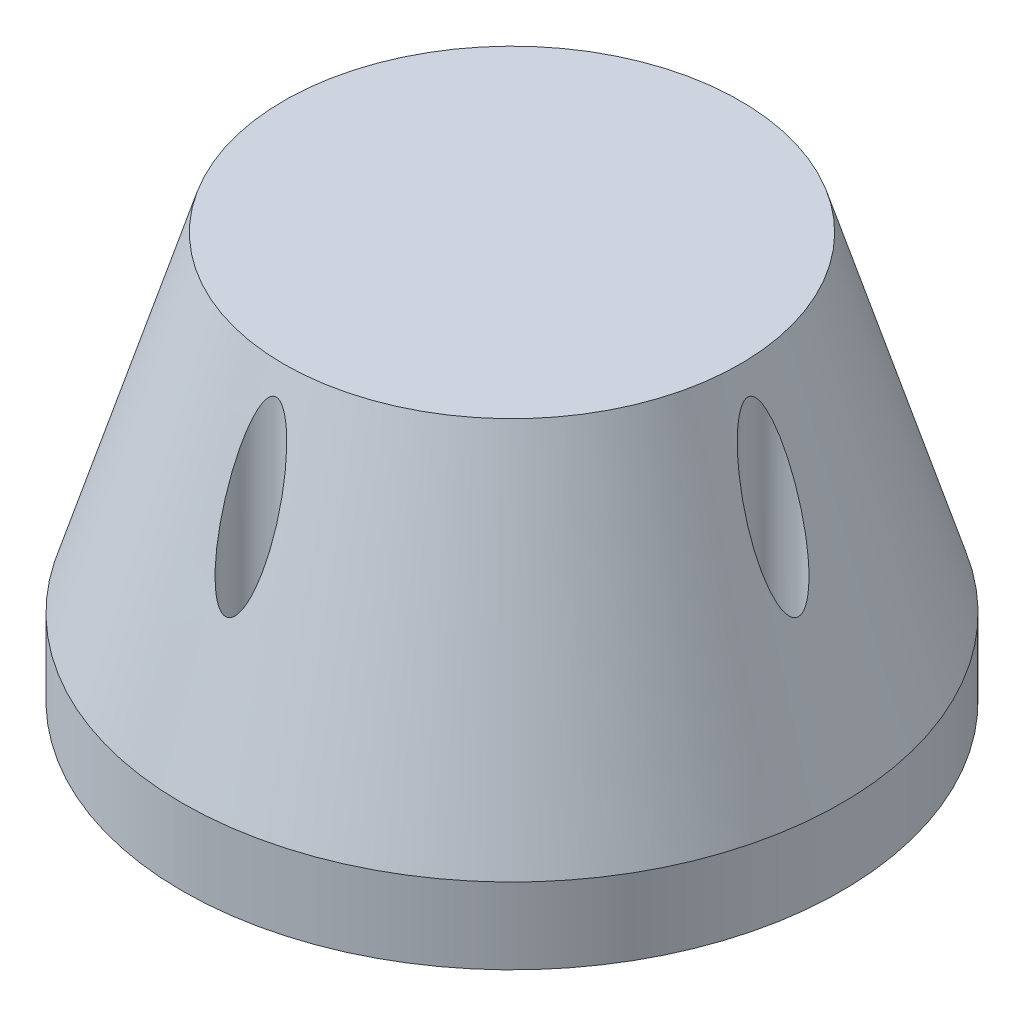
SolidWorks part; units mm, degrees
ref_plane "Front Plane" through (0, 0, 0) normal (0, 0, 1) x (1, 0, 0)
ref_plane "Top Plane" through (0, 0, 0) normal (0, 1, 0) x (1, 0, 0)
ref_plane "Right Plane" through (0, 0, 0) normal (1, 0, 0) x (0, 0, -1)
sketch "Sketch1" plane through (0, 0, 0) normal (1, 0, 0) x (0, 0, -1)
  line L0 (0, 0) -> (-65, 0)
  line L1 (-65, 0) -> (-65, 15)
  line L2 (-65, 15) -> (-45, 80)
  line L3 (-45, 80) -> (0, 80)
  line L4 (0, 80) -> (0, 0)
  dimension "D1" = 65
  dimension "D2" = 15
  dimension "D3" = 45
  dimension "D4" = 80
revolve "Revolve1" add sketch "Sketch1" angle 360 about L4
sketch "Sketch2" plane through (0, 80, 0) normal (0, 1, 0) x (1, 0, 0)
  circle A0 centre (0, 0) radius 51.5 construction
  circle A1 centre (-51.5, 0) radius 3
  circle A2 centre (0, 51.5) radius 3
  circle A3 centre (51.5, 0) radius 3
  circle A4 centre (0, -51.5) radius 3
  circle A5 centre (-51.5, 0) radius 5
  circle A6 centre (0, 51.5) radius 5
  circle A7 centre (51.5, 0) radius 5
  circle A8 centre (0, -51.5) radius 5
  point P14 (0, 0)
  point P22 (0, 0)
  dimension "D1" = 103
  dimension "D2" = 6
  dimension "D4" = 10
  dimension "D3" = 4
  dimension "D5" = 4
extrude "Cut-Extrude1" cut sketch "Sketch2" against normal through all contours A4 | A3 | A2 | A1 region at (-51.5, 80, 0) region at (0, 80, -51.5) region at (51.5, 80, 0) region at (0, 80, 51.5)
extrude "Cut-Extrude2" cut sketch "Sketch2<3>" against normal blind 45 contours A8 A4 | A7 A3 | A6 A2 | A5 A1 region at (-56.3586, 80, 0) region at (-4.8586, 80, -51.5) region at (46.6414, 80, 0) region at (-4.8586, 80, 51.5)
sketch "Sketch2<3>" plane through (0, 80, 0) normal (0, 1, 0) x (1, 0, 0) same geometry as "Sketch2"
